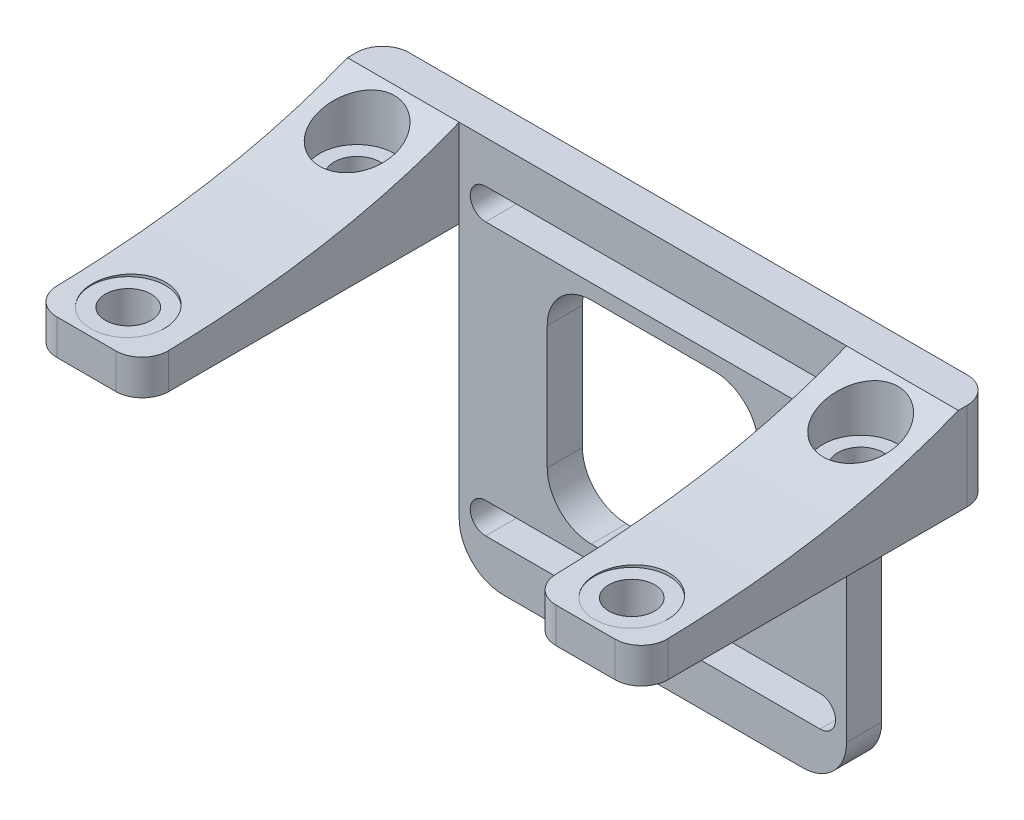
SolidWorks part; units mm, degrees
ref_plane "Front Plane" through (0, 0, 0) normal (0, 0, 1) x (1, 0, 0)
ref_plane "Top Plane" through (0, 0, 0) normal (0, 1, 0) x (1, 0, 0)
ref_plane "Right Plane" through (0, 0, 0) normal (1, 0, 0) x (0, 0, -1)
sketch "Sketch1" plane through (0, 0, 0) normal (0, 0, 1) x (1, 0, 0)
  line L0 (-19, 15.45) -> (19, 15.45) construction
  line L1 (-22, 22) -> (22, 22)
  line L2 (-22, 22) -> (-22, -22)
  line L3 (-22, -22) -> (22, -22)
  line L4 (22, 22) -> (22, -22)
  line L5 (-22, 22) -> (22, -22) construction
  line L6 (-22, -22) -> (22, 22) construction
  line L7 (7, 12) -> (-7, 12)
  line L8 (12, 7) -> (12, -7)
  line L9 (7, -12) -> (-7, -12)
  line L10 (-12, 7) -> (-12, -7)
  line L11 (12, 12) -> (-12, -12) construction
  line L12 (12, -12) -> (-12, 12) construction
  line L13 (-19, 17.2) -> (19, 17.2)
  line L14 (-19, 13.7) -> (19, 13.7)
  line L15 (0, 0) -> (50000, 0) construction
  line L16 (-19, -15.45) -> (19, -15.45) construction
  line L17 (-19, -17.2) -> (19, -17.2)
  line L18 (-19, -13.7) -> (19, -13.7)
  arc A0 (-12, -7) -> (-7, -12) centre (-7, -7) ccw
  arc A1 (7, -12) -> (12, -7) centre (7, -7) ccw
  arc A2 (12, 7) -> (7, 12) centre (7, 7) ccw
  arc A3 (-7, 12) -> (-12, 7) centre (-7, 7) ccw
  arc A4 (-19, 17.2) -> (-19, 13.7) centre (-19, 15.45) ccw
  arc A5 (19, 13.7) -> (19, 17.2) centre (19, 15.45) ccw
  arc A6 (-19, -17.2) -> (-19, -13.7) centre (-19, -15.45) cw
  arc A7 (19, -13.7) -> (19, -17.2) centre (19, -15.45) cw
  circle A8 centre (0, 0) radius 12 construction
  point P0 (0, 0)
  point P6 (0, 0)
  point P25 (0, 15.45)
  point P35 (0, -15.45)
  dimension "D4" = 5
  dimension "D1" = 44
  dimension "D2" = 44
  dimension "D3" = 24
  dimension "D5" = 38
  dimension "D6" = 1.75
  dimension "D7" = 15.45
extrude "Boss-Extrude1" add sketch "Sketch1" along normal blind 4
sketch "Sketch2" plane through (22, 0, 0) normal (1, 0, 0) x (0, 0, -1)
  line L0 (0, 12) -> (-40, 12)
  line L1 (0, -22) -> (0, 22) construction
  line L2 (0, 12) -> (0, 22)
  line L3 (0, 22) -> (-4, 22)
  line L4 (-40, 12) -> (-40, 16)
  line L5 (-40, 16) -> (0, 16) construction
  spline S0 degree 2 poles (-40, 16) (-18.3297, 16.1194) (-4, 22) knots 0 0 0 1 1 1
  dimension "D1" = 4
  dimension "D2" = 40
  dimension "D3" = 12
extrude "Boss-Extrude2" add sketch "Sketch2" along normal blind 12.7
sketch "Sketch3" plane through (0, 12, 0) normal (0, -1, 0) x (1, 0, 0)
  line L0 (34.7, 0) -> (22, 0) construction
  line L1 (34.7, 40) -> (34.7, 0) construction
  line L2 (34.7, 40) -> (22, 40) construction
  circle A0 centre (28.6, 35) radius 2.6
  circle A1 centre (28.6, 9) radius 2.6
  point P7 (0, 0)
  point P8 (0, 0)
  point P9 (0, 0)
  point P10 (0, 0)
  dimension "D2" = 5.2
  dimension "D1" = 6.1
  dimension "D3" = 5
  dimension "D4" = 9
extrude "Cut-Extrude1" cut sketch "Sketch3" against normal through all
ref_plane "Plane1" through (0, 16, 0) normal (0, -1, 0) x (-1, 0, 0)
sketch "Sketch4" plane through (0, 16, 0) normal (0, -1, 0) x (-1, 0, 0)
  circle A0 centre (-28.6, -9) radius 4.25
  circle A1 centre (-28.6, -35) radius 4.25
  dimension "D1" = 8.5
  dimension "D2" = 8.5
extrude "Cut-Extrude2" cut sketch "Sketch4" against normal through all
ref_plane "Plane2" through (0, 0, 0) normal (1, 0, 0) x (0, 0, -1)
mirror "Mirror1" about plane through (0, 0, 0) normal (1, 0, 0) of "Cut-Extrude1", "Cut-Extrude2", "Boss-Extrude2"
fillet "Fillet1" radius 3 6 edges at (34.7, 17, 0) (-34.7, 17, 0) (34.7, 14, 40) (22, 14, 40) (-22, 14, 40) (-34.7, 14, 40)
fillet "Fillet2" radius 5 2 edges at (22, -22, 2) (-22, -22, 2)
